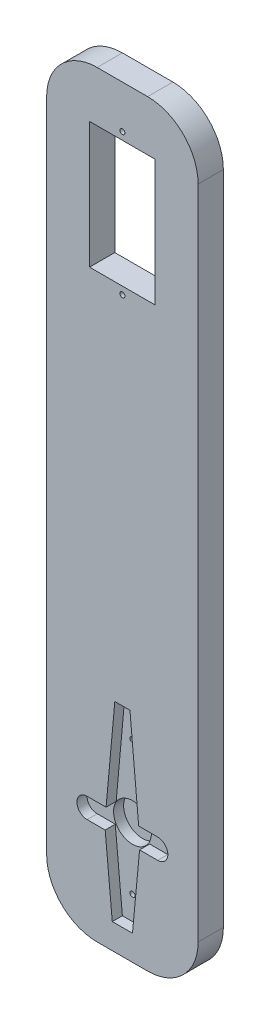
SolidWorks part; units mm, degrees
ref_plane "Přední rovina" through (0, 0, 0) normal (0, 0, 1) x (1, 0, 0)
ref_plane "Horní rovina" through (0, 0, 0) normal (0, 1, 0) x (1, 0, 0)
ref_plane "Pravá rovina" through (0, 0, 0) normal (1, 0, 0) x (0, 0, -1)
sketch "Skica1" plane through (0, 0, 0) normal (0, 0, 1) x (1, 0, 0)
  line L1 (0, 0) -> (30, 0)
  line L2 (0, 0) -> (0, 150)
  line L3 (0, 150) -> (30, 150)
  line L4 (30, 0) -> (30, 150)
  dimension "D1" = 150
  dimension "D2" = 30
extrude "Přidat vysunutím1" add sketch "Skica1" along normal blind 5
fillet "Zaoblit1" radius 10 4 edges at (30, 0, 2.5) (0, 0, 2.5) (30, 150, 2.5) (0, 150, 2.5)
sketch "Skica2" plane through (0, 0, 5) normal (0, 0, 1) x (1, 0, 0)
  line L1 (8.5, 140) -> (21.5, 140)
  line L2 (8.5, 140) -> (8.5, 115)
  line L3 (8.5, 115) -> (21.5, 115)
  line L4 (21.5, 140) -> (21.5, 115)
  line L5 (20, 150) -> (10, 150) construction
  point P4 (15, 150)
  point P7 (15, 140)
  dimension "D1" = 13
  dimension "D2" = 25
  dimension "D3" = 10
extrude "Odebrat vysunutím1" cut sketch "Skica2" against normal through all
sketch "Skica3" plane through (0, 0, 5) normal (0, 0, 1) x (1, 0, 0)
  line L0 (21.5, 140) -> (8.5, 140) construction
  line L2 (8.5, 140) -> (8.5, 115) construction
  line L3 (8.5, 127.5) -> (21.5, 127.5) construction
  line L4 (21.5, 115) -> (21.5, 140) construction
  circle A0 centre (15, 141.5) radius 0.5
  circle A1 centre (15, 113.5) radius 0.5
  point P4 (15, 140)
  point P9 (8.5, 127.5)
  dimension "D1" = 1
  dimension "D2" = 14
  dimension "D3" = 28
extrude "Odebrat vysunutím2" cut sketch "Skica3" against normal through all
sketch "Skica4" plane through (0, 0, 5) normal (0, 0, 1) x (1, 0, 0)
  line L0 (11.5, 21) -> (18.5, 21)
  line L1 (18.5, 21) -> (16.5, 43)
  line L3 (13.5, 43) -> (11.5, 21)
  line L4 (13.5, 43) -> (16.5, 43)
  line L5 (11.5, 21) -> (13, 5)
  line L6 (13, 5) -> (17, 5)
  line L7 (17, 5) -> (18.5, 21)
  line L8 (10, 0) -> (20, 0) construction
  line L10 (8, 24) -> (22, 24)
  line L11 (8, 24) -> (8, 20)
  line L12 (8, 20) -> (22, 20)
  line L13 (22, 24) -> (22, 20)
  arc A0 (8, 24) -> (8, 20) centre (8, 22) ccw
  arc A1 (22, 24) -> (22, 20) centre (22, 22) cw
  point P2 (15, 43)
  point P5 (15, 21)
  point P6 (15, 5)
  point P11 (15, 0)
  point P16 (15, 24)
  dimension "D1" = 7
  dimension "D2" = 3
  dimension "D3" = 22
  dimension "D4" = 16
  dimension "D5" = 5
  dimension "D6" = 4
  dimension "D7" = 19
  dimension "D8" = 14
  dimension "D9" = 4
extrude "Odebrat vysunutím3" cut sketch "Skica4" against normal blind 2 contours L12 L5 L6 L7 | L5 L12 L7 L0 | L11 L12 L5 L3 L10 | L10 L3 L0 L1 | L13 L10 L1 L7 L12 | A1 L13 | L11 A0 | L3 L10 L1 L4 region at (15, 22.4797, 5) region at (9.8079, 22.0229, 5) region at (15, 20.5023, 5) region at (20.1921, 22.0229, 5) region at (15, 32.3429, 5) region at (15, 13.1503, 5) region at (7.1512, 22, 5) region at (22.8488, 22, 5)
sketch "Skica5" plane through (0, 0, 3) normal (0, 0, 1) x (1, 0, 0)
  line L0 (6, 22) -> (24, 22) construction
  line L1 (13.5, 43) -> (16.5, 43) construction
  circle A0 centre (15, 36.2) radius 0.5
  circle A1 centre (15, 9.7) radius 0.5
  arc A2 (8, 24) -> (8, 20) centre (8, 22) ccw construction
  arc A3 (22, 20) -> (22, 24) centre (22, 22) ccw construction
  point P7 (0, 0)
  point P10 (15, 43)
  dimension "D1" = 1
  dimension "D2" = 1
  dimension "D4" = 14.2
  dimension "D3" = 12.3
extrude "Odebrat vysunutím4" cut sketch "Skica5" against normal through all
sketch "Skica6" plane through (0, 0, 3) normal (0, 0, 1) x (1, 0, 0)
  line L0 (6, 22) -> (24, 22) construction
  line L1 (15, 43) -> (15, 5) construction
  line L2 (13.5, 43) -> (16.5, 43) construction
  line L3 (13, 5) -> (17, 5) construction
  circle A0 centre (15, 22) radius 3.75
  arc A1 (8, 24) -> (8, 20) centre (8, 22) ccw construction
  arc A2 (22, 20) -> (22, 24) centre (22, 22) ccw construction
  point P16 (15, 22)
  dimension "D2" = 7.5
  dimension "D1" = 0
extrude "Odebrat vysunutím5" cut sketch "Skica6" against normal blind 2
